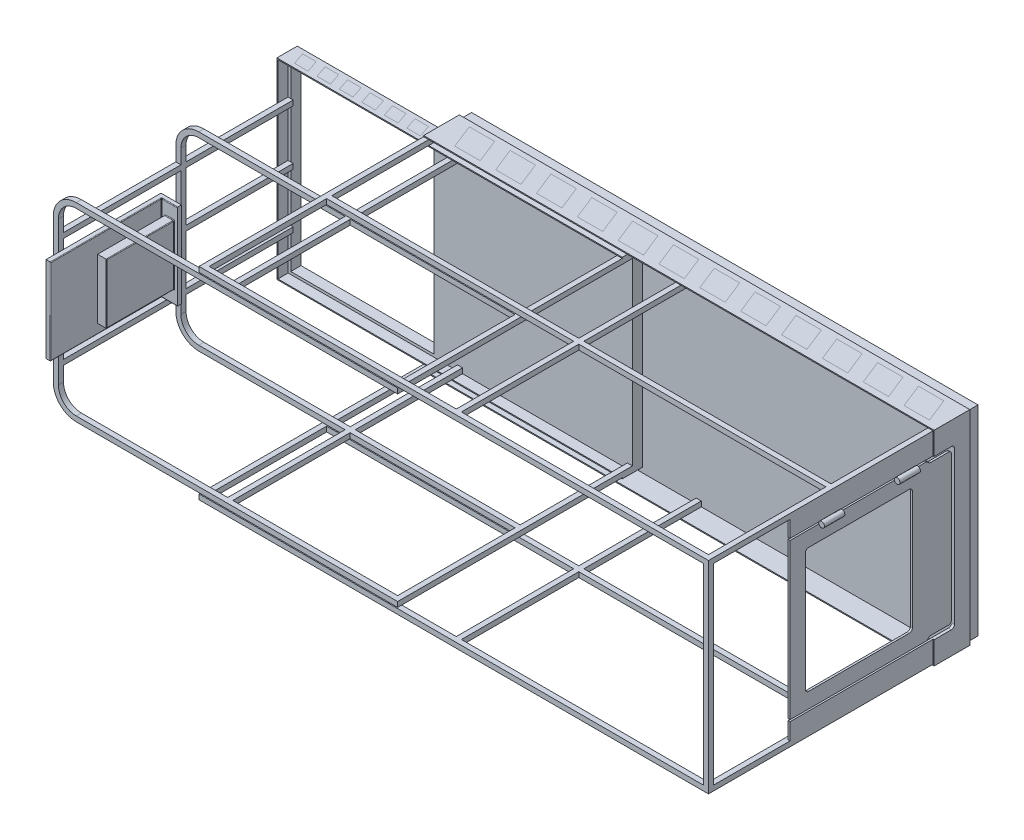
SolidWorks part; units mm, degrees
ref_plane "Front Plane" through (0, 0, 0) normal (0, 0, 1) x (1, 0, 0)
ref_plane "Top Plane" through (0, 0, 0) normal (0, 1, 0) x (1, 0, 0)
ref_plane "Right Plane" through (0, 0, 0) normal (1, 0, 0) x (0, 0, -1)
sketch "Sketch1" plane through (0, 0, 0) normal (0, 0, 1) x (1, 0, 0)
  line L1 (1250, 500) -> (-1250, 500)
  line L2 (1250, 500) -> (1250, -500)
  line L3 (1250, -500) -> (-1250, -500)
  line L4 (-1250, 500) -> (-1250, -500)
  line L5 (1250, 500) -> (-1250, -500) construction
  line L6 (1250, -500) -> (-1250, 500) construction
  point P0 (0, 0)
  dimension "D1" = 1000
  dimension "D2" = 2500
extrude "Boss-Extrude1" add sketch "Sketch1" along normal blind 75
sketch "Sketch2" plane through (0, 0, 0) normal (0, 0, -1) x (-1, 0, 0)
  line L0 (-1250, -500) -> (-1250, 500) construction
  line L1 (1250, 16.92) -> (-1250, 16.92)
  line L2 (1250, 16.92) -> (1250, -16.92)
  line L3 (1250, -16.92) -> (-1250, -16.92)
  line L4 (-1250, 16.92) -> (-1250, -16.92)
  line L5 (1250, 16.92) -> (-1250, -16.92) construction
  line L6 (1250, -16.92) -> (-1250, 16.92) construction
  point P0 (0, 0)
  dimension "D1" = 33.84
extrude "Boss-Extrude2" add sketch "Sketch2" along normal blind 300
sketch "Sketch3" plane through (0, 16.92, 0) normal (0, 1, 0) x (1, 0, 0)
  line L0 (-1250, 0) -> (1250, 0) construction
  line L1 (-1250, 300) -> (-1250, 0) construction
  circle A0 centre (-1017.6, 85.12) radius 20.5
  dimension "D1" = 41
  dimension "D2" = 85.12
  dimension "D3" = 232.4
extrude "Cut-Extrude1" cut sketch "Sketch3" against normal through all both and the other way through all
sketch "Sketch4" plane through (0, -16.92, 0) normal (0, -1, 0) x (1, 0, 0)
  line L0 (-1114.7912, 0) -> (-1096.4341, -57.4168)
  line L1 (1250, 0) -> (-1250, 0) construction
  line L2 (-976.4568, -157.8587) -> (-756.6112, 0)
  line L4 (-1250, -300) -> (-1250, 0) construction
  line L5 (-1114.7912, 0) -> (-1497.1875, 0)
  line L6 (1497.1875, 0) -> (-756.6112, 0)
  line L7 (1497.1875, 0) -> (1497.1875, -394.0557)
  line L8 (1497.1875, -394.0557) -> (-1497.1875, -394.0557)
  line L9 (-1497.1875, 0) -> (-1497.1875, -394.0557)
  arc A0 (-1096.4341, -57.4168) -> (-976.4568, -157.8587) centre (-1017.6043, -85.1321) ccw
  point P6 (-1017.6043, -85.1321)
  dimension "D1" = 83.56
  dimension "D2" = 60.28
  dimension "D3" = 72.27
  dimension "D4" = 270.65
  dimension "D5" = 358.18
  dimension "D6" = 135.2088
  dimension "D7" = 35.68
extrude "Cut-Extrude2" cut sketch "Sketch4" against normal through all and the other way through all
fillet "Fillet1" radius 250 1 edges at (-1096.4341, 0, -57.4168)
sketch "Sketch5" plane through (0, 0, 75) normal (0, 0, 1) x (1, 0, 0)
  line L0 (1250, 500) -> (-1250, 500) construction
  line L1 (1245, 495) -> (-1245, 495)
  line L2 (1245, 495) -> (1245, -495)
  line L3 (1245, -495) -> (-1245, -495)
  line L4 (-1245, 495) -> (-1245, -495)
  line L5 (1245, 495) -> (-1245, -495) construction
  line L6 (1245, -495) -> (-1245, 495) construction
  line L7 (-1250, 500) -> (-1250, -500) construction
  line L8 (1250, -500) -> (1250, 500) construction
  line L9 (-1250, -500) -> (1250, -500) construction
  line L10 (1250, -500) -> (1250, 500)
  line L11 (-1250, -500) -> (1250, -500)
  line L12 (-1250, 500) -> (-1250, -500)
  line L13 (1250, 500) -> (-1250, 500)
  point P0 (0, 0)
  dimension "D1" = 5
  dimension "D2" = 5
extrude "Boss-Extrude3" add sketch "Sketch5" along normal blind 100
sketch "Sketch6" plane through (-1250, 0, 0) normal (-1, 0, 0) x (0, 0, 1)
  line L0 (175, 500) -> (175, -500) construction
  line L1 (175, 495) -> (75, 495)
  line L2 (175, 495) -> (175, -495)
  line L3 (175, -495) -> (75, -495)
  line L4 (75, 495) -> (75, -495)
  point P6 (75, 0)
  dimension "D1" = 100
  dimension "D2" = 990
extrude "Cut-Extrude4" cut sketch "Sketch6" against normal up to surface (5 mm away) up to face at (-1245, 0, 125)
sketch "Sketch7" plane through (0, 0, 75) normal (0, 0, 1) x (1, 0, 0)
  line L0 (-15, 495) -> (-15, 470)
  line L1 (-1250, 495) -> (-1225, 495)
  line L2 (-1250, 495) -> (-1250, 470)
  line L3 (-1250, 470) -> (-1225, 470)
  line L4 (-1225, 495) -> (-1225, 470)
  line L5 (-15, 495) -> (10, 495)
  line L6 (10, 495) -> (10, 470)
  line L7 (-15, 470) -> (10, 470)
  line L8 (1220, 495) -> (1220, 470)
  line L9 (1220, 495) -> (1245, 495)
  line L10 (1245, 495) -> (1245, 470)
  line L11 (1220, 470) -> (1245, 470)
  line L12 (-15, -470) -> (-15, -495)
  line L13 (-15, -470) -> (10, -470)
  line L14 (10, -470) -> (10, -495)
  line L15 (-15, -495) -> (10, -495)
  line L16 (1220, -470) -> (1220, -495)
  line L17 (1220, -470) -> (1245, -470)
  line L18 (1245, -470) -> (1245, -495)
  line L19 (1220, -495) -> (1245, -495)
  line L20 (-1250, -470) -> (-1250, -495)
  line L21 (-1250, -470) -> (-1225, -470)
  line L22 (-1225, -470) -> (-1225, -495)
  line L23 (-1250, -495) -> (-1225, -495)
  dimension "D1" = 25
  dimension "D2" = 25
  dimension "D3" = 3
  dimension "D4" = 2
extrude "Boss-Extrude4" add sketch "Sketch7" along normal blind 1200
sketch "Sketch8" plane through (0, 0, 75) normal (0, 0, 1) x (1, 0, 0)
  line L1 (-277.22, 470) -> (-1968.62, 470)
  line L2 (-277.22, 470) -> (-277.22, -470)
  line L3 (-277.22, -470) -> (-1968.62, -470)
  line L4 (-1968.62, 470) -> (-1968.62, -470)
  line L7 (-1250, 470) -> (-1250, -470) construction
  line L8 (-1250, 470) -> (-1225, 470) construction
  line L9 (-1225, -470) -> (-1250, -470) construction
  dimension "D1" = 1691.4
  dimension "D2" = 718.62
extrude "Boss-Extrude5" add sketch "Sketch8" along normal blind 50
sketch "Sketch9" plane through (0, 0, 125) normal (0, 0, 1) x (1, 0, 0)
  line L0 (-277.22, -470) -> (-277.22, 470) construction
  line L1 (-1963.62, 465) -> (-277.22, 465)
  line L2 (-1963.62, 465) -> (-1963.62, -465)
  line L3 (-1963.62, -465) -> (-277.22, -465)
  line L5 (-1250, 470) -> (-1968.62, 470) construction
  line L6 (-1968.62, -470) -> (-1250, -470) construction
  line L7 (-1968.62, 470) -> (-1968.62, -470) construction
  line L8 (-1225, -470) -> (-1250, -470) construction
  line L9 (-1250, 470) -> (-1968.62, 470) construction
  line L10 (-1225, 470) -> (-1250, 470) construction
  line L11 (-277.22, 470) -> (-1225, 470) construction
  line L12 (-277.22, -470) -> (-277.22, 470) construction
  line L13 (-1225, -470) -> (-277.22, -470) construction
  line L14 (-1968.62, -470) -> (-1250, -470) construction
  line L15 (-1968.62, -470) -> (-1250, -470)
  line L16 (-1225, -470) -> (-1250, -470)
  line L17 (-1225, -470) -> (-277.22, -470)
  line L18 (-277.22, -470) -> (-277.22, -465)
  line L19 (-277.22, 470) -> (-1225, 470)
  line L20 (-1225, 470) -> (-1250, 470)
  line L21 (-1250, 470) -> (-1968.62, 470)
  line L22 (-1968.62, 470) -> (-1968.62, -470)
  line L23 (-277.22, 465) -> (-277.22, 470)
  dimension "D1" = 5
  dimension "D2" = 5
  dimension "D3" = 5
extrude "Boss-Extrude6" add sketch "Sketch9" along normal up to surface (50 mm away) up to face at (136.6667, 0, 175)
sketch "Sketch10" plane through (0, 0, 125) normal (0, 0, 1) x (1, 0, 0)
  line L0 (-1109.42, 465) -> (-1109.42, 440)
  line L1 (-277.22, 465) -> (-302.22, 465)
  line L2 (-277.22, 465) -> (-277.22, 440)
  line L3 (-277.22, 440) -> (-302.22, 440)
  line L4 (-302.22, 465) -> (-302.22, 440)
  line L5 (-1109.42, 465) -> (-1134.42, 465)
  line L6 (-1134.42, 465) -> (-1134.42, 440)
  line L7 (-1109.42, 440) -> (-1134.42, 440)
  line L8 (-1109.42, -440) -> (-1109.42, -465)
  line L9 (-1109.42, -440) -> (-1134.42, -440)
  line L10 (-1134.42, -440) -> (-1134.42, -465)
  line L11 (-1109.42, -465) -> (-1134.42, -465)
  line L12 (-277.22, -440) -> (-277.22, -465)
  line L13 (-277.22, -440) -> (-302.22, -440)
  line L14 (-302.22, -440) -> (-302.22, -465)
  line L15 (-277.22, -465) -> (-302.22, -465)
  line L16 (0, 0) -> (-2057.6428, 0) construction
  line L17 (-1963.62, -465) -> (-1963.62, 465) construction
  line L18 (-1963.62, -281.43) -> (-1938.62, -281.43)
  line L19 (-1963.62, -281.43) -> (-1963.62, -256.43)
  line L20 (-1963.62, -256.43) -> (-1938.62, -256.43)
  line L21 (-1938.62, -281.43) -> (-1938.62, -256.43)
  line L22 (-1963.62, 256.43) -> (-1938.62, 256.43)
  line L23 (-1938.62, 281.43) -> (-1938.62, 256.43)
  line L24 (-1963.62, 281.43) -> (-1938.62, 281.43)
  line L25 (-1963.62, 281.43) -> (-1963.62, 256.43)
  dimension "D1" = 25
  dimension "D2" = 25
  dimension "D5" = 25
  dimension "D6" = 25
  dimension "D7" = 512.86
  dimension "D3" = 2
  dimension "D4" = 2
extrude "Boss-Extrude7" add sketch "Sketch10" along normal up to surface (1150 mm away) up to face at (-1237.5, 482.5, 1275)
sketch "Sketch11" plane through (0, 0, 1275) normal (0, 0, 1) x (1, 0, 0)
  line L0 (-1250, -470) -> (-1250, -495)
  line L1 (-1250, -495) -> (1245, -495)
  line L2 (1245, -495) -> (1245, -470)
  line L3 (1245, -470) -> (-1250, -470)
  line L4 (-1250, -470) -> (-1250, -495) construction
  line L5 (-277.22, 465) -> (-277.22, 440)
  line L6 (-1250, 495) -> (1245, 495)
  line L7 (-1250, 495) -> (-1250, 470)
  line L8 (-1250, 470) -> (1245, 470)
  line L9 (1245, 495) -> (1245, 470)
  line L10 (-277.22, 440) -> (-1851.12, 440)
  line L11 (-1938.62, 256.43) -> (-1938.62, 281.43) construction
  line L12 (-1938.62, 352.5) -> (-1938.62, -352.5)
  line L14 (-1851.12, -440) -> (-277.22, -440)
  line L15 (-277.22, -440) -> (-277.22, -465)
  line L16 (-277.22, -465) -> (-1851.12, -465)
  line L17 (-1963.62, -256.43) -> (-1963.62, -281.43) construction
  line L18 (-1963.62, -352.5) -> (-1963.62, 352.5)
  line L19 (-1109.42, 465) -> (-1134.42, 465) construction
  line L20 (-1851.12, 465) -> (-277.22, 465)
  line L21 (-277.22, -465) -> (-277.22, -440) construction
  arc A0 (-1851.12, 440) -> (-1938.62, 352.5) centre (-1851.12, 352.5) ccw
  arc A1 (-1938.62, -352.5) -> (-1851.12, -440) centre (-1851.12, -352.5) ccw
  arc A2 (-1963.62, 352.5) -> (-1851.12, 465) centre (-1851.12, 352.5) cw
  arc A3 (-1851.12, -465) -> (-1963.62, -352.5) centre (-1851.12, -352.5) cw
  point P39 (-1938.62, 440)
  point P42 (-1938.62, -440)
  point P45 (-1963.62, 465)
  point P48 (-1963.62, -465)
  dimension "D1" = 87.5
  dimension "D2" = 112.5
extrude "Boss-Extrude8" add sketch "Sketch11" against normal blind 25 separate body
pattern_linear "LPattern1" count 2 spacing 600 along (0, 0, -1) of bodies 112 113 114
sketch "Sketch12" plane through (0, 0, 75) normal (0, 0, 1) x (1, 0, 0)
  line L0 (0, 0) -> (1495.4511, 0) construction
  line L1 (1245, 470) -> (1235.42, 470)
  line L2 (1245, 470) -> (1245, 388.56)
  line L3 (1245, 388.56) -> (1235.42, 388.56)
  line L4 (1235.42, 470) -> (1235.42, 388.56)
  line L5 (1245, -388.56) -> (1235.42, -388.56)
  line L6 (1235.42, -470) -> (1235.42, -388.56)
  line L7 (1245, -470) -> (1235.42, -470)
  line L8 (1245, -470) -> (1245, -388.56)
  dimension "D1" = 81.44
  dimension "D2" = 9.58
extrude "Boss-Extrude9" add sketch "Sketch12" along normal blind 800
sketch "Sketch13" plane through (1250, 0, 0) normal (1, 0, 0) x (0, 0, -1)
  line L0 (-875, -388.56) -> (-175, -388.56) construction
  line L1 (-175, 388.56) -> (-75, 388.56)
  line L2 (-175, 388.56) -> (-175, -388.56)
  line L3 (-175, -388.56) -> (-75, -388.56)
  line L4 (-75, 388.56) -> (-75, -388.56)
  dimension "D1" = 100
extrude "Cut-Extrude5" cut sketch "Sketch13" against normal blind 800
sketch "Sketch14" plane through (0, 470, 0) normal (0, -1, 0) x (1, 0, 0)
  line L1 (1220, 1275) -> (1245, 1275)
  line L2 (1220, 1275) -> (1220, 1250)
  line L3 (1220, 1250) -> (1245, 1250)
  line L4 (1245, 1275) -> (1245, 1250)
extrude "Boss-Extrude10" add sketch "Sketch14" along normal up to surface (940 mm away) up to face at (-2.5, -470, 1262.5)
sketch "Sketch15" plane through (1245, 0, 0) normal (1, 0, 0) x (0, 0, -1)
  line L0 (-875, -380.06) -> (-875, 380.06)
  line L1 (-875, -470) -> (-875, -388.56) construction
  line L2 (0, 0) -> (-1112.3652, 0) construction
  line L3 (-875, 388.56) -> (-175, 388.56) construction
  line L4 (-875, 380.06) -> (-201.46, 380.06)
  line L5 (-201.46, 380.06) -> (-201.46, 366.82)
  line L6 (-201.46, 366.82) -> (-84.3, 366.82)
  line L7 (-84.3, 366.82) -> (-84.3, -366.82)
  line L8 (-201.46, -366.82) -> (-84.3, -366.82)
  line L9 (-201.46, -380.06) -> (-201.46, -366.82)
  line L10 (-875, -380.06) -> (-201.46, -380.06)
  line L12 (-800, 305.06) -> (-276.46, 305.06)
  line L13 (-800, 305.06) -> (-800, -305.06)
  line L14 (-800, -305.06) -> (-276.46, -305.06)
  line L15 (-276.46, 305.06) -> (-276.46, -305.06)
  point P14 (-84.3, 0)
  point P17 (-875, 0)
  dimension "D1" = 8.5
  dimension "D2" = 673.54
  dimension "D3" = 117.16
  dimension "D4" = 13.24
  dimension "D5" = 75
  dimension "D6" = 75
  dimension "D7" = 75
  dimension "D8" = 523.54
extrude "Boss-Extrude11" add sketch "Sketch15" against normal blind 10 separate body
sketch "Sketch16" plane through (-1938.62, 0, 0) normal (1, 0, 0) x (0, 0, -1)
  line L0 (-1275, -495) -> (-1275, 495) construction
  line L1 (-1335.7, 210.065) -> (-772.59, 210.065)
  line L2 (-1335.7, 210.065) -> (-1335.7, -210.065)
  line L3 (-1335.7, -210.065) -> (-772.59, -210.065)
  line L4 (-772.59, 210.065) -> (-772.59, -210.065)
  point P6 (-1275, 0)
  point P7 (-1335.7, 0)
  dimension "D1" = 420.13
  dimension "D2" = 563.11
  dimension "D3" = 60.7
extrude "Boss-Extrude12" add sketch "Sketch16" along normal blind 100
sketch "Sketch17" plane through (0, 0, 125) normal (0, 0, 1) x (1, 0, 0)
  line L0 (0, 0) -> (-2396.6249, 0) construction
  line L2 (-1963.62, 12.5) -> (-1938.62, 12.5)
  line L3 (-1963.62, 12.5) -> (-1963.62, -12.5)
  line L4 (-1963.62, -12.5) -> (-1938.62, -12.5)
  line L5 (-1938.62, 12.5) -> (-1938.62, -12.5)
  line L6 (-1963.62, -256.43) -> (-1963.62, 256.43) construction
  point P7 (-1963.62, 0)
  dimension "D1" = 25
  dimension "D2" = 25
extrude "Boss-Extrude13" add sketch "Sketch17" along normal up to surface (1125 mm away) up to face at (-1946.9533, 0, 1250)
sketch "Sketch18" plane through (0, 0, 1335.7) normal (0, 0, 1) x (1, 0, 0)
  line L1 (-1838.62, 210.065) -> (-1915.62, 210.065)
  line L2 (-1838.62, 210.065) -> (-1838.62, -210.065)
  line L3 (-1838.62, -210.065) -> (-1915.62, -210.065)
  line L4 (-1915.62, 210.065) -> (-1915.62, -210.065)
  line L5 (-1838.62, -210.065) -> (-1938.62, -210.065) construction
  dimension "D1" = 77
extrude "Cut-Extrude6" cut sketch "Sketch18" against normal blind 543
sketch "Sketch19" plane through (0, 0, 772.59) normal (0, 0, -1) x (-1, 0, 0)
  line L0 (0, 0) -> (3017.7214, 0) construction
  line L1 (1898.08, 146.67) -> (1854.25, 146.67)
  line L2 (1898.08, 146.67) -> (1898.08, -146.67)
  line L3 (1898.08, -146.67) -> (1854.25, -146.67)
  line L4 (1854.25, 146.67) -> (1854.25, -146.67)
  line L5 (1838.62, -210.065) -> (1838.62, 210.065) construction
  point P7 (1854.25, 0)
  dimension "D1" = 293.34
  dimension "D2" = 43.83
  dimension "D3" = 15.63
extrude "Boss-Extrude14" add sketch "Sketch19" against normal blind 351
sketch "Sketch20" plane through (0, 0, 0) normal (0, 0, -1) x (-1, 0, 0)
  line L0 (-1250, 500) -> (1250, 500) construction
  line L1 (-1240, 490) -> (1240, 490)
  line L2 (-1240, 490) -> (-1240, -490)
  line L3 (-1240, -490) -> (1240, -490)
  line L4 (1240, 490) -> (1240, -490)
  line L5 (-1250, -500) -> (-1250, 500) construction
  line L6 (1250, -500) -> (-1250, -500) construction
  line L7 (1250, 500) -> (1250, -500) construction
  line L8 (-1230, 480) -> (-1230, -480)
  line L9 (-1230, -480) -> (1230, -480)
  line L10 (1230, 480) -> (1230, -480)
  line L11 (-1230, 480) -> (1230, 480)
  dimension "D1" = 10
  dimension "D2" = 10
  dimension "D3" = 10
  dimension "D4" = 10
  dimension "D5" = 10
extrude "Boss-Extrude15" add sketch "Sketch20" along normal blind 50
sketch "Sketch21" plane through (0, 0, 75) normal (0, 0, -1) x (-1, 0, 0)
  line L0 (1968.62, 470) -> (1968.62, -470) construction
  line L1 (1250, 452) -> (1950.62, 452)
  line L2 (1250, 452) -> (1250, -452)
  line L3 (1250, -452) -> (1950.62, -452)
  line L4 (1950.62, 452) -> (1950.62, -452)
  line L5 (1968.62, -470) -> (1250, -470) construction
  line L6 (1250, 470) -> (1968.62, 470) construction
  line L7 (1250, 470) -> (1250, -470) construction
  dimension "D1" = 18
  dimension "D2" = 18
  dimension "D3" = 18
extrude "Cut-Extrude7" cut sketch "Sketch21" against normal up to surface (50 mm away) up to face at (-1359.9771, 0, 125)
ref_plane "Plane1" through (0, 0, 735) normal (0, 0, 1) x (1, 0, 0)
sketch "Sketch22" plane through (0, 0, 735) normal (0, 0, 1) x (1, 0, 0)
  line L3 (1245, 388.56) -> (1245, 470) construction
  line L4 (1245, 380.06) -> (1245, -380.06) construction
  circle A0 centre (1259, 384.31) radius 14
  point P2 (1270.4858, 384.31)
  point P4 (1265.8534, 376.2919)
  point P5 (1265.2442, 369.9993)
  dimension "D1" = 28
  dimension "D2" = 4.25
extrude "Boss-Extrude16" add sketch "Sketch22" against normal blind 100 separate body
pattern_linear "LPattern2" count 2 spacing 370 along (0, 0, -1) of "Boss-Extrude16"
sketch "Sketch23" plane through (0, -500, 0) normal (0, -1, 0) x (1, 0, 0)
  line L0 (-1092.3372, 47.5989) -> (1092.3372, 47.5989) construction
  line L1 (0, 0) -> (0, 47.5989) construction
  text T0 "PARSA.HM-SLB-001" font "Arial Narrow" height in points 300
  point P2 (0, 0)
  point P3 (615.0687, 44.3227)
  point P7 (-372.5753, 55.9251)
  point P8 (-219.9758, 75.7736)
  point P9 (0, 0)
  point P11 (512.2566, -411.2861)
  point P12 (0, 0)
  point P13 (615.0687, 26.0454)
  point P14 (41.1498, 75.7736)
  point P15 (142.7834, 75.7736)
  point P16 (850, 46.1617)
  point P17 (1066.2406, 75.7736)
  point P18 (-1079.2155, 75.7736)
  point P19 (0, 0)
  point P20 (-1040.5573, 75.7736)
  point P21 (0, 0)
  point P23 (-1092.3372, 75.7188)
extrude "Cut-Extrude8" cut sketch "Sketch23" against normal blind 0.5
sketch "Sketch24" plane through (0, -500, 0) normal (0, -1, 0) x (1, 0, 0)
  line L0 (995.1537, 34.9251) -> (1141.1216, 34.9251)
  line L1 (995.1537, 34.9251) -> (1042.8398, 136.0197)
  line L2 (1141.1216, 34.9251) -> (1188.8077, 136.0197)
  line L3 (1042.8398, 136.0197) -> (1188.8077, 136.0197)
  line L12 (762.7026, 34.9251) -> (908.6706, 34.9251)
  line L13 (762.7026, 34.9251) -> (810.3887, 136.0197)
  line L14 (810.3887, 136.0197) -> (956.3567, 136.0197)
  line L15 (908.6706, 34.9251) -> (956.3567, 136.0197)
  line L16 (530.2516, 34.9251) -> (676.2195, 34.9251)
  line L17 (530.2516, 34.9251) -> (577.9377, 136.0197)
  line L18 (577.9377, 136.0197) -> (723.9056, 136.0197)
  line L19 (676.2195, 34.9251) -> (723.9056, 136.0197)
  line L21 (0, 0) -> (0, 411.8842) construction
  line L22 (-1250, 0) -> (1250, 0) construction
  line L23 (-1141.1216, 34.9251) -> (-1188.8077, 136.0197)
  line L24 (-1042.8398, 136.0197) -> (-1188.8077, 136.0197)
  line L25 (-995.1537, 34.9251) -> (-1042.8398, 136.0197)
  line L26 (-995.1537, 34.9251) -> (-1141.1216, 34.9251)
  line L27 (-762.7026, 34.9251) -> (-810.3887, 136.0197)
  line L28 (-810.3887, 136.0197) -> (-956.3567, 136.0197)
  line L29 (-908.6706, 34.9251) -> (-956.3567, 136.0197)
  line L30 (-762.7026, 34.9251) -> (-908.6706, 34.9251)
  line L31 (-530.2516, 34.9251) -> (-577.9377, 136.0197)
  line L32 (-577.9377, 136.0197) -> (-723.9056, 136.0197)
  line L33 (-676.2195, 34.9251) -> (-723.9056, 136.0197)
  line L34 (-530.2516, 34.9251) -> (-676.2195, 34.9251)
  dimension "D1" = 3
split line "Split Line1"
sketch "Sketch25" plane through (0, -470, 0) normal (0, -1, 0) x (1, 0, 0)
  line L0 (-1353.5098, 91.7698) -> (-1295.9625, 91.7698)
  line L1 (-1353.5098, 91.7698) -> (-1331.9389, 157.8305)
  line L2 (-1295.9625, 91.7698) -> (-1274.3917, 157.8305)
  line L3 (-1331.9389, 157.8305) -> (-1274.3917, 157.8305)
  line L4 (-1468.5098, 91.7698) -> (-1410.9625, 91.7698)
  line L5 (-1468.5098, 91.7698) -> (-1446.9389, 157.8305)
  line L6 (-1446.9389, 157.8305) -> (-1389.3917, 157.8305)
  line L7 (-1410.9625, 91.7698) -> (-1389.3917, 157.8305)
  line L8 (-1583.5098, 91.7698) -> (-1525.9625, 91.7698)
  line L9 (-1583.5098, 91.7698) -> (-1561.9389, 157.8305)
  line L10 (-1561.9389, 157.8305) -> (-1504.3917, 157.8305)
  line L11 (-1525.9625, 91.7698) -> (-1504.3917, 157.8305)
  line L12 (-1698.5098, 91.7698) -> (-1640.9625, 91.7698)
  line L13 (-1698.5098, 91.7698) -> (-1676.9389, 157.8305)
  line L14 (-1676.9389, 157.8305) -> (-1619.3917, 157.8305)
  line L15 (-1640.9625, 91.7698) -> (-1619.3917, 157.8305)
  line L16 (-1813.5098, 91.7698) -> (-1755.9625, 91.7698)
  line L17 (-1813.5098, 91.7698) -> (-1791.9389, 157.8305)
  line L18 (-1791.9389, 157.8305) -> (-1734.3917, 157.8305)
  line L19 (-1755.9625, 91.7698) -> (-1734.3917, 157.8305)
  line L20 (-1928.5098, 91.7698) -> (-1870.9625, 91.7698)
  line L21 (-1928.5098, 91.7698) -> (-1906.9389, 157.8305)
  line L22 (-1906.9389, 157.8305) -> (-1849.3917, 157.8305)
  line L23 (-1870.9625, 91.7698) -> (-1849.3917, 157.8305)
  dimension "D1" = 6
split line "Split Line2"
sketch "Sketch26" plane through (-1968.62, 0, 0) normal (-1, 0, 0) x (0, 0, 1)
  line L0 (157.5614, 445) -> (157.5614, 384.8242)
  line L1 (157.5614, 445) -> (95.7048, 421.8038)
  line L2 (157.5614, 384.8242) -> (95.7048, 361.628)
  line L3 (95.7048, 421.8038) -> (95.7048, 361.628)
  line L4 (157.5614, 345) -> (157.5614, 284.8242)
  line L5 (157.5614, 345) -> (95.7048, 321.8038)
  line L6 (95.7048, 321.8038) -> (95.7048, 261.628)
  line L7 (157.5614, 284.8242) -> (95.7048, 261.628)
  line L8 (157.5614, 245) -> (157.5614, 184.8242)
  line L9 (157.5614, 245) -> (95.7048, 221.8038)
  line L10 (95.7048, 221.8038) -> (95.7048, 161.628)
  line L11 (157.5614, 184.8242) -> (95.7048, 161.628)
  line L12 (157.5614, 145) -> (157.5614, 84.8242)
  line L13 (157.5614, 145) -> (95.7048, 121.8038)
  line L14 (95.7048, 121.8038) -> (95.7048, 61.628)
  line L15 (157.5614, 84.8242) -> (95.7048, 61.628)
  line L16 (157.5614, 45) -> (157.5614, -15.1758)
  line L17 (157.5614, 45) -> (95.7048, 21.8038)
  line L18 (95.7048, 21.8038) -> (95.7048, -38.372)
  line L19 (157.5614, -15.1758) -> (95.7048, -38.372)
  line L20 (157.5614, -55) -> (157.5614, -115.1758)
  line L21 (157.5614, -55) -> (95.7048, -78.1962)
  line L22 (95.7048, -78.1962) -> (95.7048, -138.372)
  line L23 (157.5614, -115.1758) -> (95.7048, -138.372)
  line L24 (157.5614, -155) -> (157.5614, -215.1758)
  line L25 (157.5614, -155) -> (95.7048, -178.1962)
  line L26 (95.7048, -178.1962) -> (95.7048, -238.372)
  line L27 (157.5614, -215.1758) -> (95.7048, -238.372)
  line L28 (157.5614, -255) -> (157.5614, -315.1758)
  line L29 (157.5614, -255) -> (95.7048, -278.1962)
  line L30 (95.7048, -278.1962) -> (95.7048, -338.372)
  line L31 (157.5614, -315.1758) -> (95.7048, -338.372)
  line L32 (157.5614, -355) -> (157.5614, -415.1758)
  line L33 (157.5614, -355) -> (95.7048, -378.1962)
  line L34 (95.7048, -378.1962) -> (95.7048, -438.372)
  line L35 (157.5614, -415.1758) -> (95.7048, -438.372)
  line L36 (175, 470) -> (75, 470) construction
  dimension "D2" = 25
  dimension "D1" = 9
split line "Split Line3"
sketch "Sketch27" plane through (0, 500, 0) normal (0, 1, 0) x (1, 0, 0)
  line L0 (1148.8921, -26.2218) -> (1024.768, -26.2218)
  line L1 (1148.8921, -26.2218) -> (1195.6417, -143.5844)
  line L2 (1024.768, -26.2218) -> (1071.5175, -143.5844)
  line L3 (1195.6417, -143.5844) -> (1071.5175, -143.5844)
  line L4 (948.8921, -26.2218) -> (824.768, -26.2218)
  line L5 (948.8921, -26.2218) -> (995.6417, -143.5844)
  line L6 (995.6417, -143.5844) -> (871.5175, -143.5844)
  line L7 (824.768, -26.2218) -> (871.5175, -143.5844)
  line L8 (748.8921, -26.2218) -> (624.768, -26.2218)
  line L9 (748.8921, -26.2218) -> (795.6417, -143.5844)
  line L10 (795.6417, -143.5844) -> (671.5175, -143.5844)
  line L11 (624.768, -26.2218) -> (671.5175, -143.5844)
  line L12 (548.8921, -26.2218) -> (424.768, -26.2218)
  line L13 (548.8921, -26.2218) -> (595.6417, -143.5844)
  line L14 (595.6417, -143.5844) -> (471.5175, -143.5844)
  line L15 (424.768, -26.2218) -> (471.5175, -143.5844)
  line L16 (348.8921, -26.2218) -> (224.768, -26.2218)
  line L17 (348.8921, -26.2218) -> (395.6417, -143.5844)
  line L18 (395.6417, -143.5844) -> (271.5175, -143.5844)
  line L19 (224.768, -26.2218) -> (271.5175, -143.5844)
  line L20 (148.8921, -26.2218) -> (24.768, -26.2218)
  line L21 (148.8921, -26.2218) -> (195.6417, -143.5844)
  line L22 (195.6417, -143.5844) -> (71.5175, -143.5844)
  line L23 (24.768, -26.2218) -> (71.5175, -143.5844)
  line L24 (-51.1079, -26.2218) -> (-175.232, -26.2218)
  line L25 (-51.1079, -26.2218) -> (-4.3583, -143.5844)
  line L26 (-4.3583, -143.5844) -> (-128.4825, -143.5844)
  line L27 (-175.232, -26.2218) -> (-128.4825, -143.5844)
  line L28 (-251.1079, -26.2218) -> (-375.232, -26.2218)
  line L29 (-251.1079, -26.2218) -> (-204.3583, -143.5844)
  line L30 (-204.3583, -143.5844) -> (-328.4825, -143.5844)
  line L31 (-375.232, -26.2218) -> (-328.4825, -143.5844)
  line L32 (-451.1079, -26.2218) -> (-575.232, -26.2218)
  line L33 (-451.1079, -26.2218) -> (-404.3583, -143.5844)
  line L34 (-404.3583, -143.5844) -> (-528.4825, -143.5844)
  line L35 (-575.232, -26.2218) -> (-528.4825, -143.5844)
  line L36 (-651.1079, -26.2218) -> (-775.232, -26.2218)
  line L37 (-651.1079, -26.2218) -> (-604.3583, -143.5844)
  line L38 (-604.3583, -143.5844) -> (-728.4825, -143.5844)
  line L39 (-775.232, -26.2218) -> (-728.4825, -143.5844)
  line L40 (-851.1079, -26.2218) -> (-975.232, -26.2218)
  line L41 (-851.1079, -26.2218) -> (-804.3583, -143.5844)
  line L42 (-804.3583, -143.5844) -> (-928.4825, -143.5844)
  line L43 (-975.232, -26.2218) -> (-928.4825, -143.5844)
  line L44 (-1051.1079, -26.2218) -> (-1175.232, -26.2218)
  line L45 (-1051.1079, -26.2218) -> (-1004.3583, -143.5844)
  line L46 (-1004.3583, -143.5844) -> (-1128.4825, -143.5844)
  line L47 (-1175.232, -26.2218) -> (-1128.4825, -143.5844)
  dimension "D1" = 12
split line "Split Line4"
sketch "Sketch28" plane through (0, 470, 0) normal (0, 1, 0) x (1, 0, 0)
  line L0 (-1306.0843, -94.8201) -> (-1372.8378, -94.8201)
  line L1 (-1306.0843, -94.8201) -> (-1285.8429, -154.8689)
  line L2 (-1372.8378, -94.8201) -> (-1352.5964, -154.8689)
  line L3 (-1285.8429, -154.8689) -> (-1352.5964, -154.8689)
  line L4 (-1416.0843, -94.8201) -> (-1482.8378, -94.8201)
  line L5 (-1416.0843, -94.8201) -> (-1395.8429, -154.8689)
  line L6 (-1395.8429, -154.8689) -> (-1462.5964, -154.8689)
  line L7 (-1482.8378, -94.8201) -> (-1462.5964, -154.8689)
  line L8 (-1526.0843, -94.8201) -> (-1592.8378, -94.8201)
  line L9 (-1526.0843, -94.8201) -> (-1505.8429, -154.8689)
  line L10 (-1505.8429, -154.8689) -> (-1572.5964, -154.8689)
  line L11 (-1592.8378, -94.8201) -> (-1572.5964, -154.8689)
  line L12 (-1636.0843, -94.8201) -> (-1702.8378, -94.8201)
  line L13 (-1636.0843, -94.8201) -> (-1615.8429, -154.8689)
  line L14 (-1615.8429, -154.8689) -> (-1682.5964, -154.8689)
  line L15 (-1702.8378, -94.8201) -> (-1682.5964, -154.8689)
  line L16 (-1746.0843, -94.8201) -> (-1812.8378, -94.8201)
  line L17 (-1746.0843, -94.8201) -> (-1725.8429, -154.8689)
  line L18 (-1725.8429, -154.8689) -> (-1792.5964, -154.8689)
  line L19 (-1812.8378, -94.8201) -> (-1792.5964, -154.8689)
  line L20 (-1856.0843, -94.8201) -> (-1922.8378, -94.8201)
  line L21 (-1856.0843, -94.8201) -> (-1835.8429, -154.8689)
  line L22 (-1835.8429, -154.8689) -> (-1902.5964, -154.8689)
  line L23 (-1922.8378, -94.8201) -> (-1902.5964, -154.8689)
  dimension "D1" = 6
split line "Split Line5"
fillet "Fillet2" radius 15 8 edges at (1240, -305.06, 800) (1240, -305.06, 276.46) (1240, 305.06, 800) (1240, 305.06, 276.46) (1240, -366.82, 84.3) (1240, 366.82, 84.3) (1240, -366.82, 201.46) (1240, 366.82, 201.46)
fillet "Fillet3" radius 3 14 edges at (-1877.12, 210.065, 792.7) (-1877.12, -210.065, 792.7) (-1876.165, -146.67, 792.7) (-1876.165, 146.67, 792.7) (-1915.62, 210.065, 1064.2) (-1915.62, 0, 792.7) (-1915.62, -210.065, 1064.2) (-1915.62, 0, 1335.7) (-1854.25, -146.67, 958.145) (-1854.25, 0, 1123.59) (-1854.25, 146.67, 958.145) (-1854.25, 0, 792.7) (-1938.62, -12.5, 1011.295) (-1938.62, 12.5, 1011.295)
fillet "Fillet4" radius 15 2 edges at (1240, 380.06, 201.46) (1240, -380.06, 201.46)
fillet "Fillet5" radius 15 2 edges at (1242.71, -388.56, 75) (1242.71, 388.56, 75)
